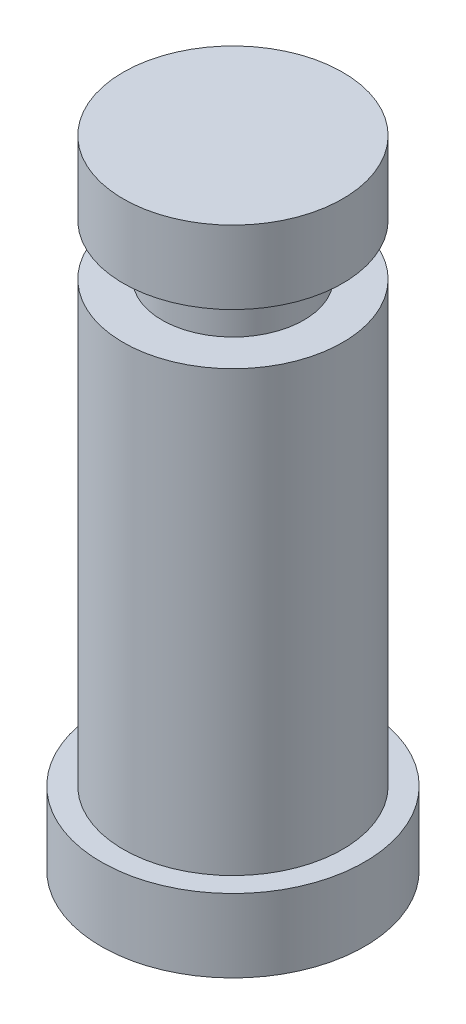
SolidWorks part; units mm, degrees
material "K110"
ref_plane "Front Plane" through (0, 0, 0) normal (0, 0, 1) x (1, 0, 0)
ref_plane "Top Plane" through (0, 0, 0) normal (0, 1, 0) x (1, 0, 0)
ref_plane "Right Plane" through (0, 0, 0) normal (1, 0, 0) x (0, 0, -1)
sketch "Sketch1" plane through (0, 0, 0) normal (0, 0, 1) x (1, 0, 0)
  line L0 (0, 0) -> (9, 0)
  line L1 (9, 0) -> (9, 5)
  line L2 (9, 5) -> (7.5, 5)
  line L3 (7.5, 5) -> (7.5, 43.5)
  line L4 (7.5, 43.5) -> (0, 43.5)
  line L5 (0, 43.5) -> (0, 0)
  line L6 (0, 48.5) -> (0, -5) construction
  point P9 (8.25, 5)
  dimension "D1" = 5
  dimension "D2" = 5
  dimension "D3" = 18
  dimension "D4" = 15
  dimension "D5" = 5
  dimension "D6" = 38.5
revolve "Revolve1" add sketch "Sketch1" angle 360 about L6
sketch "Sketch2" plane through (0, 0, 0) normal (0, 0, 1) x (1, 0, 0)
  line L0 (7.5, 5) -> (7.5, 43.5) construction
  line L1 (7.5, 35) -> (4.85, 35)
  line L2 (7.5, 35) -> (7.5, 38.5)
  line L3 (7.5, 38.5) -> (4.85, 38.5)
  line L4 (4.85, 35) -> (4.85, 38.5)
  line L5 (0, 43.5) -> (0, 5) construction
  line L6 (7.5, 43.5) -> (-7.5, 43.5) construction
  line L7 (9, 5) -> (-9, 5) construction
  dimension "D1" = 3.5
  dimension "D2" = 2.65
  dimension "D3" = 30
revolve "Cut-Revolve1" cut sketch "Sketch2" angle 360 about L5
